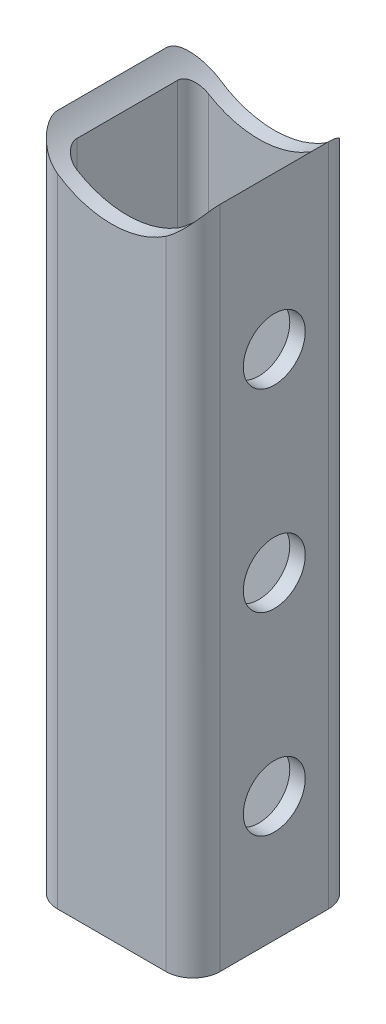
SolidWorks part; units mm, degrees
material "1060 Сплав"
ref_plane "Спереди" through (0, 0, 0) normal (0, 0, 1) x (1, 0, 0)
ref_plane "Сверху" through (0, 0, 0) normal (0, 1, 0) x (1, 0, 0)
ref_plane "Справа" through (0, 0, 0) normal (1, 0, 0) x (0, 0, -1)
sketch "Эскиз1" plane through (0, 0, 0) normal (0, 1, 0) x (1, 0, 0)
  line L1 (-6.993, -10.5) -> (6.993, -10.5)
  line L2 (-10.5, -6.993) -> (-10.5, 6.993)
  line L3 (-6.993, 10.5) -> (6.993, 10.5)
  line L4 (10.5, -6.993) -> (10.5, 6.993)
  line L5 (-10.5, -10.5) -> (10.5, 10.5) construction
  line L6 (-10.5, 10.5) -> (10.5, -10.5) construction
  line L7 (6.5, 8.5) -> (-6.5, 8.5)
  line L8 (8.5, 6.5) -> (8.5, -6.5)
  line L9 (6.5, -8.5) -> (-6.5, -8.5)
  line L10 (-8.5, 6.5) -> (-8.5, -6.5)
  line L11 (8.5, 8.5) -> (-8.5, -8.5) construction
  line L12 (8.5, -8.5) -> (-8.5, 8.5) construction
  arc A0 (-6.5, -8.5) -> (-8.5, -6.5) centre (-6.5, -6.5) cw
  arc A1 (8.5, 6.5) -> (6.5, 8.5) centre (6.5, 6.5) ccw
  arc A2 (-8.5, 6.5) -> (-6.5, 8.5) centre (-6.5, 6.5) cw
  arc A3 (6.5, -8.5) -> (8.5, -6.5) centre (6.5, -6.5) ccw
  arc A4 (-10.5, -6.993) -> (-6.993, -10.5) centre (-6.993, -6.993) ccw
  arc A5 (6.993, -10.5) -> (10.5, -6.993) centre (6.993, -6.993) ccw
  arc A6 (10.5, 6.993) -> (6.993, 10.5) centre (6.993, 6.993) ccw
  arc A7 (-10.5, 6.993) -> (-6.993, 10.5) centre (-6.993, 6.993) cw
  point P0 (0, 0)
  point P5 (0, 0)
  dimension "D4" = 2
  dimension "D5" = 2
  dimension "D6" = 3.507
  dimension "D1" = 21
  dimension "D2" = 21
  dimension "D3" = 17
extrude "Бобышка-Вытянуть1" add sketch "Эскиз1" along normal blind 110
sketch "Эскиз2" plane through (0, 0, -10.5) normal (0, 0, -1) x (-1, 0, 0)
  circle A0 centre (0, 112.5) radius 12.5
  dimension "D1" = 112.5
extrude "Вырез-Вытянуть1" cut sketch "Эскиз2" against normal through all
sketch "Эскиз3" plane through (10.5, 0, 0) normal (1, 0, 0) x (0, 0, -1)
  circle A0 centre (0, 36) radius 4
  circle A1 centre (0, 61) radius 4
  circle A2 centre (0, 86) radius 4
  dimension "D1" = 8
  dimension "D2" = 25
  dimension "D3" = 25
  dimension "D4" = 36
extrude "Вырез-Вытянуть2" cut sketch "Эскиз3" against normal through all
sketch "Эскиз4" plane through (0, 0, 10.5) normal (0, 0, 1) x (1, 0, 0)
  line L0 (-10.5, 105.7177) -> (-10.5, 0) construction
  line L1 (-10.5, -0.1083) -> (22.3359, -0.1083)
  line L2 (-10.5, -0.1083) -> (-10.5, 19.8917)
  line L3 (-10.5, 19.8917) -> (22.3359, 19.8917)
  line L4 (22.3359, -0.1083) -> (22.3359, 19.8917)
  dimension "D1" = 20
extrude "Вырез-Вытянуть4" cut sketch "Эскиз4" against normal through all contours L4 L3 L2 L1
